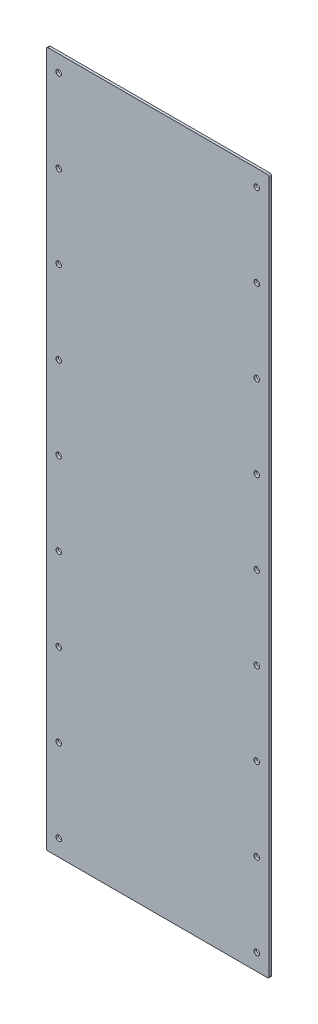
SolidWorks part; units mm, degrees
material "3.3547 (EN-AW 5083)"
ref_plane "Front Plane" through (0, 0, 0) normal (0, 0, 1) x (1, 0, 0)
ref_plane "Top Plane" through (0, 0, 0) normal (0, 1, 0) x (1, 0, 0)
ref_plane "Right Plane" through (0, 0, 0) normal (1, 0, 0) x (0, 0, -1)
sketch "Sketch1" plane through (0, 0, 0) normal (0, 0, 1) x (1, 0, 0)
  line L1 (-135, 0) -> (135, 0)
  line L2 (-135, 0) -> (-135, 843)
  line L3 (-135, 843) -> (135, 843)
  line L4 (135, 0) -> (135, 843)
  dimension "D1" = 270
  dimension "D2" = 843
base flange "Base-Flange1" sketch "Sketch1" thickness 3 reverse thickness direction no parameters "D1"=0.7366
hole_wizard "M6 Clearance Hole1" positions "Sketch7" profile "Sketch8" hole size "M6" standard "DIN" end condition up to next
sketch "Sketch7" plane through (0, 0, 0) normal (0, 0, 1) x (1, 0, 0)
  line L18 (-120, 15) -> (120, 15)
  line L19 (120, 15) -> (120, 828)
  line L20 (120, 828) -> (-120, 828)
  line L21 (-120, 828) -> (-120, 15)
  line L25 (-120, 823) -> (-120, 20)
  line L50 (135, 843) -> (-135, 843) construction
  line L51 (-135, 0) -> (135, 0) construction
  point P37 (-120, 20)
  dimension "D2" = 20
  dimension "D3" = 20
  dimension "D1" = 15
sketch "Sketch8" plane through (-120, 20, 0) normal (1, 0, 0) x (0, -1, 0)
  line L0 (0, 0) -> (0, 3)
  line L1 (0, 3) -> (3.3, 3)
  line L2 (3.3, 3) -> (3.3, 0.025)
  line L3 (3.3, 0.025) -> (3.325, 0)
  line L5 (3.325, 0) -> (0, 0)
  line L6 (-3.3, 0.025) -> (-3.325, 0) construction
  line L11 (0, -6.35) -> (0, 107.95) construction
  dimension "Thru Hole Dia." = 6.6
  dimension "Thru Hole Depth" = 3
  dimension "Near C'Sink Dia." = 6.65
  dimension "Near C'Sink Angle" = 90
pattern_curve "CrvPattern2" of "M6 Clearance Hole1" parameters "D1"=9, "D3"=50, "D2"=1, "D4"=50
mirror "Mirror1" about plane through (0, 0, 0) normal (1, 0, 0) of "CrvPattern2", "M6 Clearance Hole1"
fillet "Fillet1" radius 2 4 edges at (-135, 843, -1.5) (135, 843, -1.5) (135, 0, -1.5) (-135, 0, -1.5)
sketch "Bend-Lines1" [suppressed] plane through (0, 0, 0) normal (0, 1, 0) x (1, 0, 0)
sketch "Bounding-Box1" [suppressed] plane through (0, 0, 0) normal (0, 1, 0) x (1, 0, 0)
sheet metal parameters "Sheet-Metal1" thickness 3 parameters "D1"=0.7366
flat pattern "Flat-Pattern1" [suppressed]
sketch "Bend-Lines2" plane through (0, 0, 0) normal (0, 1, 0) x (1, 0, 0)
sketch3d "Bounding-Box2" [suppressed]
  line L0 (-200, 700, 0) -> (-200, 0, 0) construction
  line L1 (0, 700, 0) -> (0, 0, 0) construction
  line L2 (-200, 700, 0) -> (0, 700, 0) construction
  line L3 (-200, 0, 0) -> (0, 0, 0) construction
sheet metal parameters "Sheet-Metal2" thickness 3 parameters "D1"=0.7366
flat pattern "Flat-Pattern1"
sketch "Bend-Lines2" plane through (0, 0, 0) normal (0, 1, 0) x (1, 0, 0)
sketch3d "Bounding-Box2" [suppressed]
  line L0 (135, 857, 0) -> (135, 0, 0) construction
  line L1 (-135, 857, 0) -> (-135, 0, 0) construction
  line L2 (135, 857, 0) -> (-135, 857, 0) construction
  line L3 (135, 0, 0) -> (-135, 0, 0) construction
sheet metal parameters "Sheet-Metal5" thickness 3 parameters "D1"=0.7366
flat pattern "Flat-Pattern1"
sketch "Bend-Lines2" plane through (0, 0, 0) normal (0, 1, 0) x (1, 0, 0)
sketch3d "Bounding-Box2" [suppressed]
  line L0 (134.9995, 0, 0) -> (135, 843, 0) construction
  line L1 (-135, 0.0001, 0) -> (-134.9995, 843.0001, 0) construction
  line L2 (134.9995, 0, 0) -> (-135, 0.0001, 0) construction
  line L3 (135, 843, 0) -> (-134.9995, 843.0001, 0) construction
sheet metal parameters "Sheet-Metal6" thickness 3 parameters "D1"=0.7366
flat pattern "Flat-Pattern1"
sketch "Bend-Lines2" plane through (0, 0, 0) normal (0, 1, 0) x (1, 0, 0)
sketch3d "Bounding-Box2" [suppressed]
  line L0 (135, 857, 0) -> (135, 0, 0) construction
  line L1 (-135, 857, 0) -> (-135, 0, 0) construction
  line L2 (135, 857, 0) -> (-135, 857, 0) construction
  line L3 (135, 0, 0) -> (-135, 0, 0) construction
